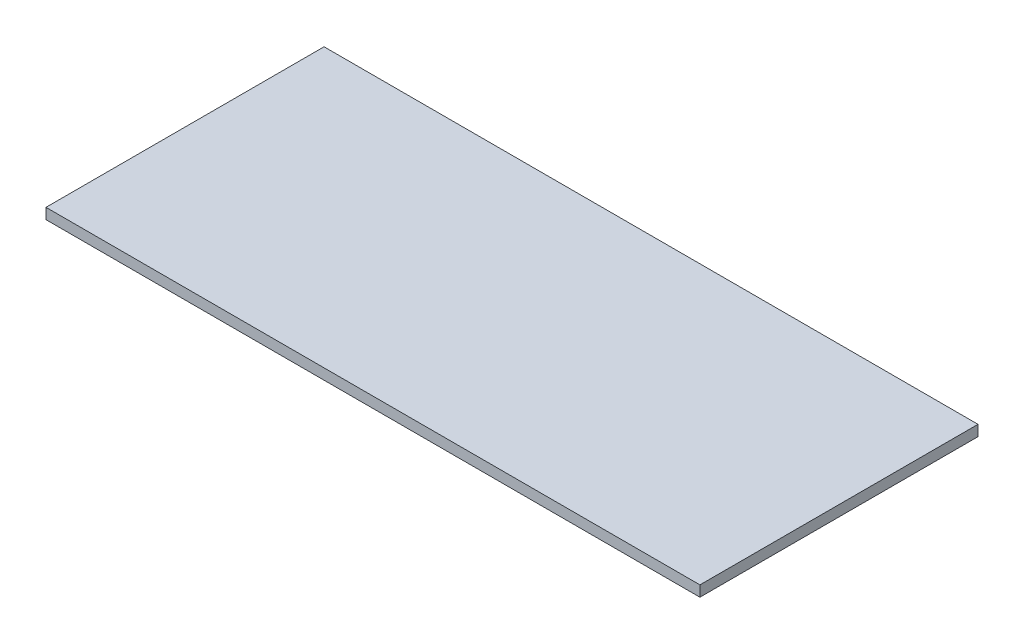
SolidWorks part; units mm, degrees
material "有机玻璃 (TM) GS 丙烯酸铸钣"
ref_plane "前视基准面" through (0, 0, 0) normal (0, 0, 1) x (1, 0, 0)
ref_plane "上视基准面" through (0, 0, 0) normal (0, 1, 0) x (1, 0, 0)
ref_plane "右视基准面" through (0, 0, 0) normal (1, 0, 0) x (0, 0, -1)
other "Configuration Table"
sketch "草图2" plane through (0, 0, 0) normal (0, 1, 0) x (1, 0, 0)
  line L1 (-50.7602, 28.1287) -> (34.2398, 28.1287)
  line L2 (-50.7602, 28.1287) -> (-50.7602, -12.2222)
  line L3 (-50.7602, -12.2222) -> (34.2398, -12.2222)
  line L4 (34.2398, 28.1287) -> (34.2398, -12.2222)
  dimension "D1" = 85
extrude "凸台-拉伸2" add sketch "草图2" along normal blind 4
sketch "草图3" plane through (0, 0, 0) normal (0, 1, 0) x (1, 0, 0)
  line L0 (7.1413, -3.4232) -> (7.1413, 7.9531)
  line L1 (-24.8308, 8.4531) -> (-42.5646, 8.4531)
  line L2 (-42.5646, 8.4531) -> (-42.5646, 7.4531)
  line L3 (-50.7602, 7.9532) -> (34.2398, 7.9532) construction
  line L5 (-50.7602, 28.1287) -> (-50.7602, -12.2222) construction
  line L6 (34.2398, -12.2222) -> (34.2398, 28.1287) construction
  line L7 (-41.7602, 28.1287) -> (-41.7602, -12.2222) construction
  line L8 (34.2398, 28.1287) -> (-50.7602, 28.1287) construction
  line L9 (-50.7602, 7.9532) -> (34.2398, 28.1287) construction
  line L10 (-50.7602, -12.2222) -> (34.2398, -12.2222) construction
  line L37 (-15.3527, 19.5935) -> (-15.3527, 15.492) construction
  line L38 (-16.8587, 8.4531) -> (-16.8587, 19.5935)
  line L39 (-12.3595, -3.831) -> (-12.3595, 0.4856) construction
  line L40 (-13.8587, 19.4043) -> (-13.8587, -3.9638)
  line L41 (-9.3527, 19.5935) -> (-9.3527, 15.492) construction
  line L42 (-10.8587, -3.9448) -> (-10.8587, 19.5173)
  line L43 (-6.3518, -3.5978) -> (-6.3518, 1.8831) construction
  line L44 (-7.8587, 19.3895) -> (-7.8587, -3.6497)
  line L45 (2.6473, 19.5935) -> (2.6473, 15.6307) construction
  line L46 (-4.8587, -3.8077) -> (-4.8587, 19.5493)
  line L47 (5.6473, -3.6155) -> (5.6473, 0.4856) construction
  line L48 (-1.8587, 19.5493) -> (-1.8587, -3.6784)
  line L49 (-22.5958, 8.4531) -> (-41.7602, 18.0409)
  line L50 (1.1413, -3.6811) -> (1.1413, 19.5173)
  line L51 (-0.3587, -3.6702) -> (-0.3587, 1.308) construction
  line L52 (4.1413, 19.3895) -> (4.1413, -3.6497)
  line L53 (-41.7602, 18.0409) -> (-42.2077, 17.1466)
  line L54 (-15.8587, 8.4531) -> (-15.8587, 19.5935)
  line L55 (-3.3587, 19.5493) -> (-3.3587, 15.6307) construction
  line L56 (-14.8587, 19.4842) -> (-14.8587, -4.0024)
  line L57 (-9.8587, -3.9778) -> (-9.8587, 19.5493)
  line L58 (-8.8587, 19.4756) -> (-8.8587, -3.6648)
  line L59 (-3.8587, -3.8688) -> (-3.8587, 19.5493)
  line L60 (-2.8587, 19.5493) -> (-2.8587, -3.6808)
  line L61 (2.1413, -3.6842) -> (2.1413, 19.5493)
  line L62 (3.1413, 19.4756) -> (3.1413, -3.6597)
  line L63 (8.1413, -3.3672) -> (8.1413, 7.4531)
  line L64 (8.1413, -3.3672) -> (8.1413, 9.1975) construction
  line L65 (7.1413, -3.4232) -> (7.1413, 9.1975) construction
  line L66 (7.1413, 7.9531) -> (7.1413, 8.4531)
  line L67 (-15.8587, 8.4531) -> (-15.8587, 7.4531)
  line L68 (-16.8587, 8.4531) -> (-22.5958, 8.4531)
  line L70 (-22.5958, 7.4531) -> (-15.8587, 7.4531)
  line L71 (7.1413, 8.4531) -> (22.9398, 8.4531)
  line L72 (22.9398, 8.4531) -> (22.9398, 7.4531)
  line L73 (22.9398, 7.4531) -> (8.3327, 7.4531)
  line L74 (8.1413, 7.4531) -> (8.3327, 7.4531)
  line L75 (-42.2077, 17.1466) -> (-24.8308, 8.4531)
  line L76 (34.2398, 7.9532) -> (-50.7602, 28.1287) construction
  line L77 (-8.2602, 18.0409) -> (-50.7602, 18.0409) construction
  line L78 (-24.8648, 7.4531) -> (-42.5646, 7.4531)
  line L79 (-50.7602, 7.9532) -> (34.2398, -12.2222) construction
  line L80 (34.2398, 7.9532) -> (-50.7602, -12.2222) construction
  line L81 (-8.1638, -2.1574) -> (-50.7602, -2.1574) construction
  line L82 (-22.5958, 7.4531) -> (-41.7602, -2.1574)
  line L83 (-41.7602, -2.1574) -> (-42.566, -1.4438)
  line L84 (-42.566, -1.4438) -> (-24.8648, 7.4531)
  arc A6 (-16.8587, 19.5935) -> (-13.8587, 19.4043) centre (-15.3527, 19.5935) cw
  arc A7 (-13.8587, -3.9638) -> (-10.8587, -3.9448) centre (-12.3595, -3.831) ccw
  arc A8 (-7.8587, 19.3895) -> (-10.8587, 19.5173) centre (-9.3527, 19.5935) ccw
  arc A9 (-7.8587, -3.6497) -> (-4.8587, -3.8077) centre (-6.3518, -3.5978) ccw
  arc A10 (-4.8587, 19.5493) -> (-1.8587, 19.5493) centre (-3.3587, 19.5493) cw
  arc A11 (1.1413, 19.5173) -> (4.1413, 19.3895) centre (2.6473, 19.5935) cw
  arc A12 (-1.8587, -3.6784) -> (1.1413, -3.6811) centre (-0.3587, -3.6702) ccw
  arc A13 (4.1413, -3.6497) -> (7.1413, -3.4232) centre (5.6473, -3.6155) ccw
  arc A14 (-15.8587, 19.5935) -> (-14.8587, 19.4842) centre (-15.3527, 19.5935) cw
  arc A15 (-14.8587, -4.0024) -> (-9.8587, -3.9778) centre (-12.3595, -3.831) ccw
  arc A16 (-8.8587, 19.4756) -> (-9.8587, 19.5493) centre (-9.3527, 19.5935) ccw
  arc A17 (-8.8587, -3.6648) -> (-3.8587, -3.8688) centre (-6.3518, -3.5978) ccw
  arc A18 (-3.8587, 19.5493) -> (-2.8587, 19.5493) centre (-3.3587, 19.5493) cw
  arc A19 (-2.8587, -3.6808) -> (2.1413, -3.6842) centre (-0.3587, -3.6702) ccw
  arc A20 (2.1413, 19.5493) -> (3.1413, 19.4756) centre (2.6473, 19.5935) cw
  arc A21 (3.1413, -3.6597) -> (8.1413, -3.3672) centre (5.6473, -3.6155) ccw
  dimension "D1" = 1
  dimension "D2" = 0.5
  dimension "D8" = 1
extrude "切除-拉伸9" cut sketch "草图3" along normal blind 2
sketch "草图4" plane through (0, 0, 0) normal (0, 1, 0) x (1, 0, 0)
  line L0 (-50.7602, 7.9532) -> (34.2398, 7.9532) construction
  line L1 (-50.7602, 7.9532) -> (34.2398, 28.1287) construction
  line L2 (-8.2602, 18.0409) -> (-50.7602, 18.0409) construction
  line L3 (-50.7602, 28.1287) -> (-50.7602, -12.2222) construction
  line L4 (-50.7602, 18.0409) -> (34.2398, 18.0409) construction
  line L5 (-8.2602, -2.1345) -> (-50.7602, -2.1345) construction
  line L6 (34.2398, -12.2222) -> (34.2398, 28.1287) construction
  line L7 (34.2398, 7.9532) -> (-50.7602, 28.1287) construction
  line L8 (-50.7602, 7.9532) -> (34.2398, -12.2222) construction
  line L9 (-50.7602, -12.2222) -> (34.2398, 7.9532) construction
  line L10 (-50.7602, -2.1345) -> (34.2398, -2.1345) construction
  line L11 (-43.7602, 28.1287) -> (-43.7602, -12.2222) construction
  line L12 (34.2398, 28.1287) -> (-50.7602, 28.1287) construction
  line L13 (-50.7602, -12.2222) -> (34.2398, -12.2222) construction
  circle A1 centre (-43.7602, 18.0409) radius 2
  circle A2 centre (-43.7602, 7.9532) radius 2
  circle A3 centre (-43.7602, -2.1345) radius 2
  dimension "D1" = 7
extrude "切除-拉伸13" cut sketch "草图4" along normal blind 2
sketch "草图8" plane through (0, 0, 0) normal (0, 1, 0) x (1, 0, 0)
  line L0 (24.7398, 28.1287) -> (24.7398, -12.2222) construction
  line L1 (34.2398, 28.1287) -> (-50.7602, 28.1287) construction
  line L2 (-50.7602, -12.2222) -> (34.2398, -12.2222) construction
  line L3 (34.2398, -12.2222) -> (34.2398, 28.1287) construction
  line L4 (-50.7602, 7.9532) -> (34.2398, 7.9532) construction
  line L5 (-50.7602, 28.1287) -> (-50.7602, -12.2222) construction
  circle A0 centre (24.7398, 7.9532) radius 2
  dimension "D1" = 9.5
extrude "切除-拉伸14" cut sketch "草图8" along normal blind 2
sketch "草图9" plane through (0, 0, 0) normal (0, 1, 0) x (1, 0, 0)
  line L0 (-43.7602, 28.1287) -> (-43.7602, -12.5071) construction
  line L1 (34.2398, 28.1287) -> (-50.7602, 28.1287) construction
  line L2 (-50.7602, 28.1287) -> (-50.7602, -12.2222) construction
  line L3 (-50.7602, 7.9532) -> (34.2398, 7.9532) construction
  line L4 (34.2398, -12.2222) -> (34.2398, 28.1287) construction
  line L5 (34.2398, 7.9532) -> (-50.7602, 28.1287) construction
  line L6 (-50.7602, 7.9532) -> (34.2398, 28.1287) construction
  line L7 (-50.7602, 7.9532) -> (34.2398, -12.2222) construction
  line L8 (34.2398, 7.9532) -> (-50.7602, -12.2222) construction
  line L9 (-8.2602, 18.0409) -> (-50.7602, 18.0409) construction
  line L10 (-50.7602, 18.0409) -> (34.2398, 18.0409) construction
  line L11 (-8.2602, -2.1345) -> (-50.7602, -2.1345) construction
  line L12 (-50.7602, -2.1345) -> (34.2398, -2.1345) construction
  line L13 (24.7398, 28.1287) -> (24.7398, -12.2222) construction
  circle A0 centre (-43.7602, 18.0409) radius 1.7
  circle A1 centre (-43.7602, 7.9532) radius 1.7
  circle A2 centre (-43.7602, -2.1345) radius 1.7
  circle A3 centre (24.7398, 7.9532) radius 1.7
  dimension "D2" = 9.5
  dimension "D1" = 7
extrude "切除-拉伸15" cut sketch "草图9" along normal blind 4
fillet "圆角6" radius 1 1 edges at (-42.011, 1, 1.1649)
fillet "圆角9" radius 50 1 edges at (-41.7602, 1, 2.1574)
fillet "圆角11" radius 1 1 edges at (-41.7604, 1, 2.1573)
fillet "圆角12" radius 1 1 edges at (22.8033, 1, -7.4531)
fillet "圆角13" radius 1 1 edges at (22.8032, 1, -8.4531)
fillet "圆角14" radius 1 1 edges at (8.1413, 1, -7.4531)
fillet "圆角15" radius 1 1 edges at (7.1413, 1, -8.4531)
fillet "圆角16" radius 1 1 edges at (-16.8587, 1, -8.4531)
fillet "圆角17" radius 1 1 edges at (-15.8587, 1, -7.4531)
fillet "圆角18" radius 1 1 edges at (-22.5958, 1, -8.4531)
fillet "圆角19" radius 1 1 edges at (-22.5958, 1, -7.4531)
fillet "圆角23" radius 0.1 1 edges at (-24.8648, 1, -7.4531)
fillet "圆角24" radius 0.1 1 edges at (-24.8308, 1, -8.4531)
fillet "圆角25" radius 1 1 edges at (-41.7602, 1, -18.0409)
fillet "圆角26" radius 1 1 edges at (-42.0211, 1, -17.0533)
fillet "圆角27" radius 1 1 edges at (-41.8237, 1, -8.4531)
fillet "圆角28" radius 1 1 edges at (-41.8238, 1, -7.4531)
ref_plane "基准面1" through (0, 4, 0) normal (0, 1, 0) x (1, 0, 0)
sketch "草图11" plane through (0, 4, 0) normal (0, 1, 0) x (1, 0, 0)
  line L0 (-50.7602, 28.1287) -> (34.2398, -12.2222) construction
  line L5 (34.2398, 28.1287) -> (-50.7602, -12.2222) construction
  line L7 (-69.32, 33.9182) -> (52.7995, 33.9182)
  line L8 (-69.32, 33.9182) -> (-69.32, -18.0118)
  line L9 (-69.32, -18.0118) -> (52.7995, -18.0118)
  line L10 (52.7995, 33.9182) -> (52.7995, -18.0118)
  line L11 (-69.32, 33.9182) -> (52.7995, -18.0118) construction
  line L12 (-69.32, -18.0118) -> (52.7995, 33.9182) construction
  point P6 (-8.2602, 7.9532)
extrude "凸台-拉伸4" add sketch "草图11" along normal blind 2 separate body
